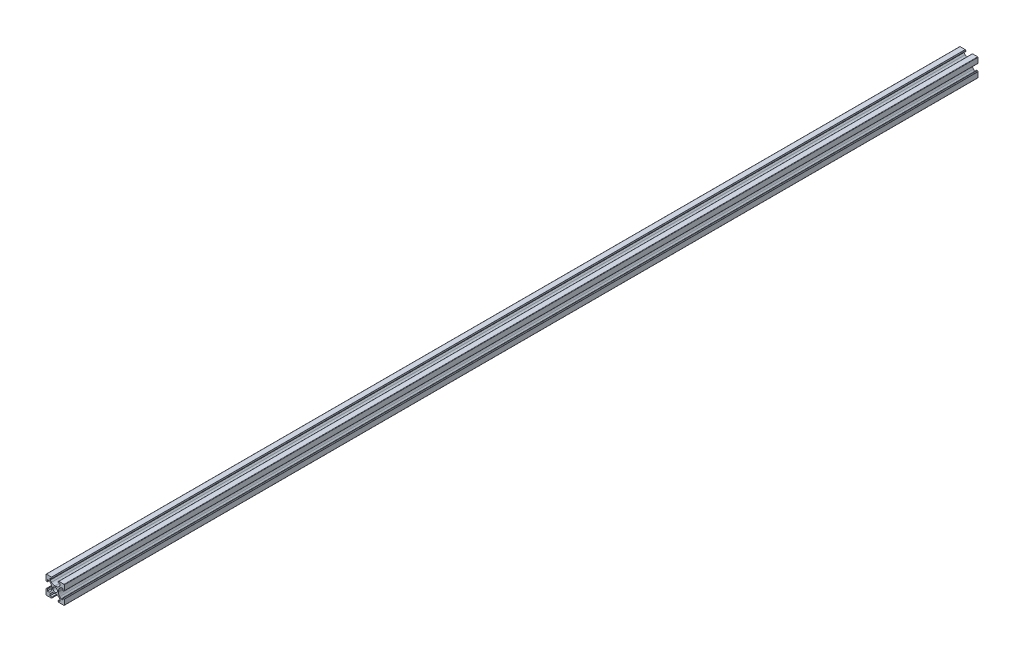
SolidWorks part; units mm, degrees
material "6063-O"
ref_plane "Plano frontal" through (0, 0, 0) normal (0, 0, 1) x (1, 0, 0)
ref_plane "Plano superior" through (0, 0, 0) normal (0, 1, 0) x (1, 0, 0)
ref_plane "Plano direito" through (0, 0, 0) normal (1, 0, 0) x (0, 0, -1)
sketch "Esboço1" plane through (0, 0, 0) normal (0, 0, 1) x (1, 0, 0)
  line L0 (-9.0343, 3.1) -> (-8.9, 3.1)
  line L3 (-10, 10) -> (-4.0657, 10)
  line L5 (-10, -10) -> (10, 10) construction
  line L6 (-10, 10) -> (10, -10) construction
  line L7 (-8.5, 3.5) -> (-8.5, 5.5)
  line L8 (-10, 0) -> (10, 0) construction
  line L9 (0, 10) -> (0, -10) construction
  line L12 (-8.5, 5.5) -> (-6.5607, 5.5)
  line L15 (-6.5607, 5.5) -> (-5.0645, 4.0038)
  line L16 (-3.6, 0.4683) -> (-3.6, 0)
  line L17 (-0.4683, 3.6) -> (0, 3.6)
  line L18 (-5.5, 6.5607) -> (-4.0038, 5.0645)
  line L21 (-5.5, 8.5) -> (-5.5, 6.5607)
  line L24 (-3.5, 8.5) -> (-5.5, 8.5)
  line L25 (-3.1, 9.0343) -> (-3.1, 8.9)
  line L44 (-10, 4.0657) -> (-10, 10)
  line L45 (-9.8828, 3.7828) -> (-9.3172, 3.2172)
  line L46 (-3.7828, 9.8828) -> (-3.2172, 9.3172)
  line L47 (-3.6, 0) -> (-2.5, 0)
  line L48 (0, 3.6) -> (0, 2.5)
  arc A0 (-3.5, 8.5) -> (-3.1, 8.9) centre (-3.5, 8.9) ccw
  arc A1 (-3.7828, 9.8828) -> (-4.0657, 10) centre (-4.0657, 9.6) ccw
  arc A2 (-10, 4.0657) -> (-9.8828, 3.7828) centre (-9.6, 4.0657) ccw
  arc A3 (-8.5, 3.5) -> (-8.9, 3.1) centre (-8.9, 3.5) cw
  arc A4 (-3.2172, 9.3172) -> (-3.1, 9.0343) centre (-3.5, 9.0343) cw
  arc A5 (-9.3172, 3.2172) -> (-9.0343, 3.1) centre (-9.0343, 3.5) ccw
  arc A6 (-3.6, 0.4683) -> (-5.0645, 4.0038) centre (-8.6, 0.4683) ccw
  arc A7 (-4.0038, 5.0645) -> (-0.4683, 3.6) centre (-0.4683, 8.6) ccw
  circle A8 centre (0, 0) radius 2.5
  point P6 (-10, 3.1)
  point P28 (-3.1, 8.5)
  point P31 (-3.1, 10)
  point P33 (-3.9, 10)
  point P36 (-10, 3.9)
  point P39 (-8.5, 3.1)
  point P42 (-3.1, 9.2)
  point P45 (-9.2, 3.1)
  point P48 (-3.6, 2.5393)
  point P51 (-2.5393, 3.6)
  dimension "D5" = 10
  dimension "D9" = 0.4
  dimension "D10" = 0.4
  dimension "D11" = 5
  dimension "D12" = 5
  dimension "D13" = 5
  dimension "D1" = 6.9
  dimension "D2" = 1.5
  dimension "D3" = 3.6
  dimension "D4" = 1.5
  dimension "D6" = 2.4
  dimension "D7" = 3.6
  dimension "D8" = 45
extrude "Ressalto-extrusão1" add sketch "Esboço1" along normal blind 1000 contours A4 A3 L3 A0 L17 L18 L21 L24 L25 L0 L7 L12 L15 L16 region at (-5.9987, 5.9987, 0)
sketch "Esboço3" plane through (0, 0, 0) normal (1, 0, 0) x (0, 0, -1)
  line L0 (0, 0) -> (-1000, 0) construction
  dimension "D1" = 1000
pattern_circular "PadrãoCircular1" count 4 every 90 about axis through (0, 0, 0) along (0, 0, 1) of "Ressalto-extrusão1"
fillet "Filete1" radius 0.4 4 edges at (-10, -10, 500) (-10, 10, 500) (10, -10, 500) (10, 10, 500)
